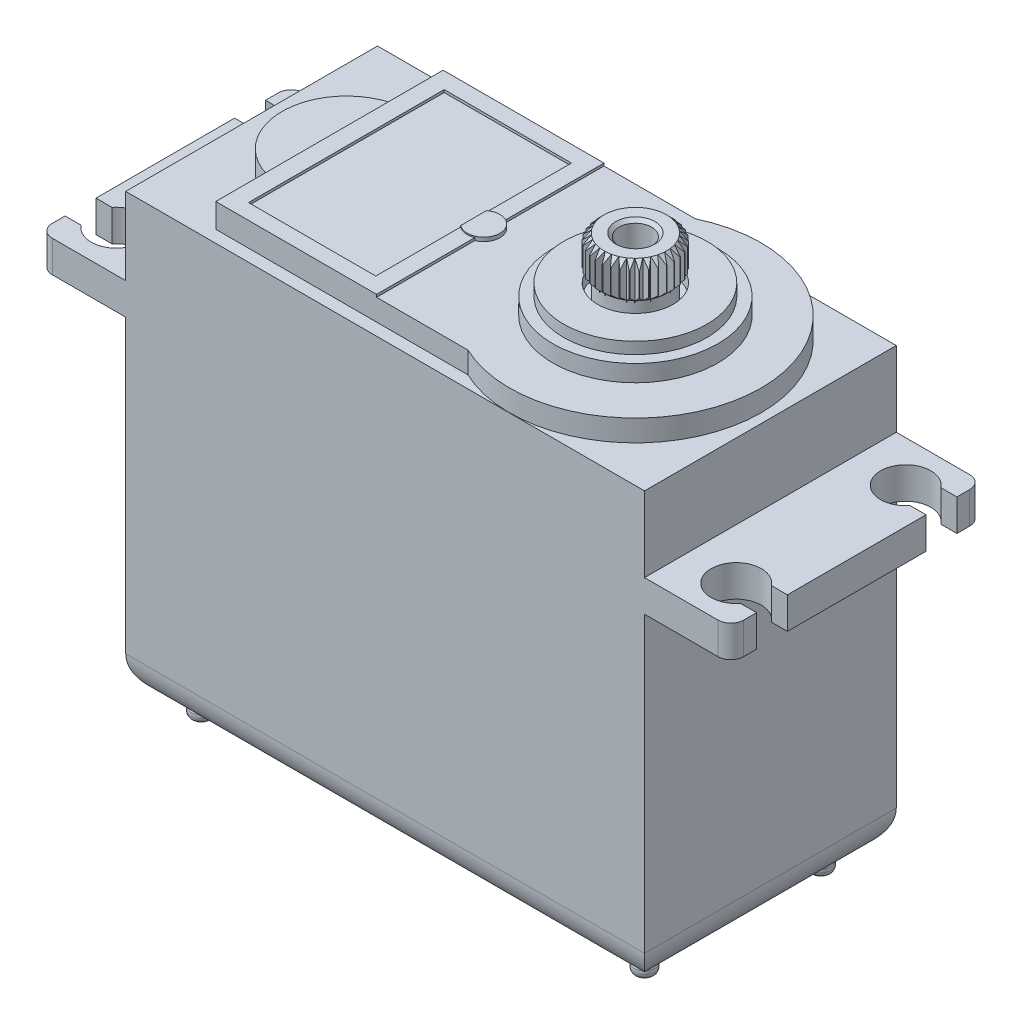
SolidWorks part; units mm, degrees
ref_plane "Front Plane" through (0, 0, 0) normal (0, 0, 1) x (1, 0, 0)
ref_plane "Top Plane" through (0, 0, 0) normal (0, 1, 0) x (1, 0, 0)
ref_plane "Right Plane" through (0, 0, 0) normal (1, 0, 0) x (0, 0, -1)
sketch "Sketch1" plane through (0, 0, 0) normal (0, 1, 0) x (1, 0, 0)
  line L1 (-18.6567, 11.3793) -> (21.6633, 11.3793)
  line L2 (-18.6567, 11.3793) -> (-18.6567, -8.1907)
  line L3 (-18.6567, -8.1907) -> (21.6633, -8.1907)
  line L4 (21.6633, 11.3793) -> (21.6633, -8.1907)
extrude "Boss-Extrude1" add sketch "Sketch1" along normal blind 35.37
sketch "Sketch2" plane through (21.6633, 0, 0) normal (1, 0, 0) x (0, 0, -1)
  line L0 (-8.1907, 0) -> (-8.1907, 3)
  line L1 (-8.1907, 35.37) -> (-8.1907, 0) construction
  line L2 (-8.1907, 3) -> (-5.1907, 0)
  line L3 (-8.1907, 0) -> (11.3793, 0) construction
  line L4 (-5.1907, 0) -> (-8.1907, 0)
  line L5 (1.5943, 0) -> (1.5943, 35.37) construction
  line L6 (-8.1907, 35.37) -> (11.3793, 35.37) construction
  line L7 (8.3793, 0) -> (11.3793, 0)
  line L8 (11.3793, 3) -> (8.3793, 0)
  line L9 (11.3793, 0) -> (11.3793, 3)
extrude "Cut-Extrude1" cut sketch "Sketch2" against normal up to next
sketch "Sketch3" plane through (0, 0, 8.1907) normal (0, 0, 1) x (1, 0, 0)
  line L0 (21.6633, 0) -> (18.6633, 0)
  line L1 (-18.6567, 0) -> (21.6633, 0) construction
  line L2 (18.6633, 0) -> (21.6633, 3)
  line L3 (21.6633, 35.37) -> (21.6633, 3) construction
  line L4 (21.6633, 3) -> (21.6633, 0)
  line L5 (1.5033, 35.37) -> (1.5033, 0) construction
  line L6 (-18.6567, 35.37) -> (21.6633, 35.37) construction
  line L7 (-18.6567, 3) -> (-18.6567, 0)
  line L8 (-15.6567, 0) -> (-18.6567, 3)
  line L9 (-18.6567, 0) -> (-15.6567, 0)
extrude "Cut-Extrude2" cut sketch "Sketch3" against normal up to next
fillet "Fillet2" radius 3 4 edges at (21.6633, 3, -1.5943) (1.5033, 3, 8.1907) (-18.6567, 3, -1.5943) (1.5033, 3, -11.3793)
sketch "Sketch5" plane through (21.6633, 0, 0) normal (1, 0, 0) x (0, 0, -1)
  line L0 (1.5943, 35.37) -> (1.5943, 29.53) construction
  line L1 (-8.1907, 35.37) -> (11.3793, 35.37) construction
  line L2 (-8.1907, 29.53) -> (1.5943, 29.53)
  line L3 (-8.1907, 35.37) -> (-8.1907, 4.2426) construction
  line L4 (1.5943, 29.53) -> (11.3793, 29.53)
  line L5 (11.3793, 35.37) -> (11.3793, 4.2426) construction
  line L6 (11.3793, 29.53) -> (11.3793, 27.07)
  line L7 (11.3793, 27.07) -> (-8.1907, 27.07)
  line L8 (-8.1907, 27.07) -> (-8.1907, 29.53)
extrude "Boss-Extrude2" add sketch "Sketch5" along normal blind 6.71
sketch "Sketch7" plane through (-18.6567, 0, 0) normal (-1, 0, 0) x (0, 0, 1)
  line L0 (-1.5943, 35.37) -> (-1.5943, 29.3613) construction
  line L1 (-11.3793, 29.3613) -> (-1.5943, 29.3613)
  line L2 (-1.5943, 29.3613) -> (8.1907, 29.3613)
  line L3 (8.1907, 29.3613) -> (8.1907, 26.9013)
  line L4 (8.1907, 26.9013) -> (-11.3793, 26.9013)
  line L5 (-11.3793, 26.9013) -> (-11.3793, 29.3613)
  line L6 (-11.3793, 35.37) -> (8.1907, 35.37) construction
  line L7 (8.1907, 35.37) -> (8.1907, 4.2426) construction
  line L8 (-11.3793, 35.37) -> (-11.3793, 4.2426) construction
extrude "Boss-Extrude3" add sketch "Sketch7" along normal blind 6.71
sketch "Sketch8" plane through (0, 29.53, 0) normal (0, 1, 0) x (1, 0, 0)
  line L0 (28.3733, 1.5943) -> (-25.3667, 1.5943) construction
  line L2 (-25.3667, -8.1907) -> (-25.3667, 11.3793) construction
  line L4 (28.3733, -3.7925) -> (27.1303, -3.7925)
  line L5 (28.3733, 11.3793) -> (28.3733, -8.1907) construction
  line L6 (28.3733, 8.181) -> (28.3733, 9.381)
  line L7 (28.3733, 9.381) -> (27.1303, 9.381)
  line L8 (28.3733, 8.181) -> (28.3733, 6.981)
  line L9 (28.3733, 6.981) -> (27.1303, 6.981)
  line L10 (28.3733, -4.9925) -> (28.3733, -3.7925)
  line L11 (28.3733, -6.1925) -> (27.1303, -6.1925)
  line L12 (28.3733, -4.9925) -> (28.3733, -6.1925)
  line L13 (1.5033, 11.3793) -> (1.5033, -8.1907) construction
  line L14 (21.6633, 11.3793) -> (-18.6567, 11.3793) construction
  line L15 (-18.6567, -8.1907) -> (21.6633, -8.1907) construction
  line L24 (-25.3667, 6.981) -> (-24.1237, 6.981)
  line L25 (-25.3667, -4.9925) -> (-25.3667, -6.1925)
  line L26 (-25.3667, -6.1925) -> (-24.1237, -6.1925)
  line L27 (-25.3667, -4.9925) -> (-25.3667, -3.7925)
  line L28 (-25.3667, -3.7925) -> (-24.1237, -3.7925)
  line L29 (-25.3667, 8.181) -> (-25.3667, 6.981)
  line L30 (-25.3667, 9.381) -> (-24.1237, 9.381)
  line L31 (-25.3667, 8.181) -> (-25.3667, 9.381)
  arc A0 (27.1303, -3.7925) -> (27.1303, -6.1925) centre (25.5933, -4.9925) ccw
  arc A1 (27.1303, 6.981) -> (27.1303, 9.381) centre (25.5933, 8.181) cw
  arc A4 (-24.1237, 6.981) -> (-24.1237, 9.381) centre (-22.5867, 8.181) ccw
  arc A5 (-24.1237, -3.7925) -> (-24.1237, -6.1925) centre (-22.5867, -4.9925) cw
extrude "Cut-Extrude3" cut sketch "Sketch8" against normal up to next
sketch "Sketch9" plane through (0, 35.37, 0) normal (0, 1, 0) x (1, 0, 0)
  line L0 (6.9933, -8.1907) -> (6.9933, -7.2426) construction
  line L1 (-18.6567, 6.4311) -> (-12.6067, 6.4311) construction
  line L2 (6.9933, 11.3793) -> (6.9933, 10.4311) construction
  line L3 (-18.6567, -3.2426) -> (-12.6067, -3.2426) construction
  line L4 (-18.6567, -8.1907) -> (-18.6567, 11.3793) construction
  line L5 (-18.6567, 1.5943) -> (21.6633, 1.5943) construction
  line L6 (-12.6067, 10.4311) -> (6.9933, 10.4311)
  line L7 (-18.6567, 11.3793) -> (-18.6567, -8.1907) construction
  line L8 (-12.6067, -7.2426) -> (-12.6067, -3.2426)
  line L9 (21.6633, -8.1907) -> (21.6633, 11.3793) construction
  line L10 (-12.6067, 10.4311) -> (-12.6067, 6.4311)
  line L11 (-12.6067, -7.2426) -> (6.9933, -7.2426)
  line L12 (21.6633, 1.5943) -> (20.9438, 1.5943) construction
  line L13 (21.6633, 11.3793) -> (-18.6567, 11.3793) construction
  arc A0 (6.9933, 10.4311) -> (6.9933, -7.2426) centre (11.1697, 1.5943) cw
  arc A1 (-12.6067, 6.4311) -> (-12.6067, -3.2426) centre (-11.2767, 1.5943) ccw
extrude "Boss-Extrude4" add sketch "Sketch9" along normal blind 1.67
sketch "Sketch10" plane through (0, 37.04, 0) normal (0, 1, 0) x (1, 0, 0)
  circle A1 centre (11.1697, 1.5943) radius 6.415
extrude "Boss-Extrude5" add sketch "Sketch10" along normal blind 1.3
sketch "Sketch11" plane through (0, 38.34, 0) normal (0, 1, 0) x (-1, 0, 0)
  circle A2 centre (-11.1697, -1.5943) radius 5.575
extrude "Boss-Extrude6" add sketch "Sketch11" along normal blind 0.9
sketch "Sketch12" plane through (0, 39.24, 0) normal (0, 1, 0) x (1, 0, 0)
  circle A1 centre (11.1697, 1.5943) radius 2.925
extrude "Cut-Extrude4" cut sketch "Sketch12" against normal blind 1
sketch "Sketch13" plane through (0, 38.24, 0) normal (0, 1, 0) x (-1, 0, 0)
  circle A0 centre (-11.1697, -1.5943) radius 2.425
extrude "Boss-Extrude7" add sketch "Sketch13" along normal blind 1.5
sketch "Sketch14" plane through (0, 39.74, 0) normal (0, 1, 0) x (1, 0, 0)
  circle A0 centre (11.1697, 1.5943) radius 2.925
extrude "Boss-Extrude8" add sketch "Sketch14" along normal blind 2.86
sketch "Sketch15" plane through (0, 42.6, 0) normal (0, 1, 0) x (1, 0, 0)
  circle A0 centre (11.1697, 1.5943) radius 1.27
extrude "Cut-Extrude5" cut sketch "Sketch15" against normal blind 7
sketch "Sketch16" plane through (0, 37.04, 0) normal (0, 1, 0) x (1, 0, 0)
  line L0 (-12.6067, -7.2426) -> (6.9933, -7.2426) construction
  line L1 (-12.6067, 10.4311) -> (-0.1067, 10.4311)
  line L2 (-12.6067, 10.4311) -> (-12.6067, -7.2426)
  line L3 (-12.6067, -7.2426) -> (-0.1067, -7.2426)
  line L4 (-0.1067, 10.4311) -> (-0.1067, -7.2426)
  line L5 (-6.3168, 9.1673) -> (-6.3567, 10.4311) construction
  line L6 (-11.2628, 9.1673) -> (-1.3708, 9.1673)
  line L7 (-11.2628, 9.1673) -> (-11.2628, -6.0433)
  line L8 (-11.2628, -6.0433) -> (-1.3708, -6.0433)
  line L9 (-1.3708, 9.1673) -> (-1.3708, 1.562)
  line L10 (-11.2628, 1.562) -> (-12.6067, 1.5943) construction
  line L11 (-1.3708, 1.562) -> (-0.1067, 1.5943) construction
  line L12 (-6.3168, -6.0433) -> (-6.3567, -7.2426) construction
  line L13 (-1.3708, 1.562) -> (-1.3708, -6.0433)
extrude "Boss-Extrude9" add sketch "Sketch16" along normal blind 0.2
sketch "Sketch17" plane through (0, 37.24, 0) normal (0, 1, 0) x (-1, 0, 0)
  line L0 (1.3708, -1.562) -> (1.3708, -2.562)
  line L1 (1.3708, 6.0433) -> (1.3708, -9.1673) construction
  line L2 (1.3708, -1.562) -> (1.3708, -0.562)
  arc A0 (1.3708, -2.562) -> (1.3708, -0.562) centre (0.592, -1.562) cw
extrude "Boss-Extrude10" add sketch "Sketch17" along normal blind 0.1 and the other way blind 0.5
sketch "Sketch19" plane through (0, 42.6, 0) normal (0, 1, 0) x (1, 0, 0)
  line L0 (10.8404, 4.5007) -> (11.3402, 4.5143) construction
  line L1 (11.3402, 4.5143) -> (11.0903, 4.0075)
  line L2 (11.0903, 4.0075) -> (10.8404, 4.5007)
  line L3 (11.0903, 4.5075) -> (11.0903, 4.0075) construction
  line L4 (10.8404, 4.5007) -> (10.7613, 4.6463)
  line L5 (11.3402, 4.5143) -> (11.4053, 4.6463)
  line L6 (10.7613, 4.6463) -> (11.4053, 4.6463)
  circle A3 centre (11.1697, 1.5943) radius 2.925 construction
  circle A4 centre (11.1697, 1.5943) radius 2.925 construction
extrude "Cut-Extrude11" cut sketch "Sketch19" against normal blind 3
sketch "Sketch21" plane through (0, 0, 0) normal (0, -1, 0) x (1, 0, 0)
  line L0 (1.5033, 5.1907) -> (1.5033, -8.3793) construction
  line L1 (20.7846, 7.3121) -> (17.7846, 7.3121)
  line L2 (20.7846, 7.3121) -> (20.7846, 4.3121)
  line L3 (20.7846, 4.3121) -> (17.7846, 4.3121)
  line L4 (17.7846, 7.3121) -> (17.7846, 4.3121)
  line L5 (-15.6567, 5.1907) -> (18.6633, 5.1907) construction
  line L6 (-15.6567, -8.3793) -> (18.6633, -8.3793) construction
  line L7 (-15.6567, -1.5943) -> (18.6633, -1.5943) construction
  line L8 (-15.6567, -8.3793) -> (-15.6567, 5.1907) construction
  line L9 (18.6633, -8.3793) -> (18.6633, 5.1907) construction
  line L10 (17.7846, -10.5006) -> (17.7846, -7.5006)
  line L11 (20.7846, -7.5006) -> (17.7846, -7.5006)
  line L12 (20.7846, -10.5006) -> (20.7846, -7.5006)
  line L13 (20.7846, -10.5006) -> (17.7846, -10.5006)
  line L14 (-17.778, -7.5006) -> (-14.778, -7.5006)
  line L15 (-14.778, -10.5006) -> (-14.778, -7.5006)
  line L16 (-14.778, 7.3121) -> (-14.778, 4.3121)
  line L17 (-17.778, 4.3121) -> (-14.778, 4.3121)
  line L18 (-17.778, -10.5006) -> (-14.778, -10.5006)
  line L19 (-17.778, -10.5006) -> (-17.778, -7.5006)
  line L20 (-17.778, 7.3121) -> (-17.778, 4.3121)
  line L21 (-17.778, 7.3121) -> (-14.778, 7.3121)
extrude "Cut-Extrude12" cut sketch "Sketch21" against normal blind 1
fillet "Fillet4" radius 1 4 edges at (-14.778, 0.5, -7.5006) (-14.778, 0.5, 4.3121) (17.7846, 0.5, -7.5006) (17.7846, 0.5, 4.3121)
fillet "Fillet5" radius 1 4 edges at (-25.3667, 28.1313, 8.1907) (-25.3667, 28.1313, -11.3793) (28.3733, 28.3, -11.3793) (28.3733, 28.3, 8.1907)
chamfer "Chamfer2" distance 0.5 angle 45 2 edges at (11.2493, 42.6, 1.3297) (11.2493, 39.74, 1.3297)
chamfer "Chamfer3" distance 0.25 angle 45 1 edges at (11.1697, 42.6, -0.3243)
pattern_circular "CirPattern12" count 34 over 360 about axis through (11.1697, 42.6, -1.5943) along (0, -1, 0) of "Cut-Extrude11"
sketch "Sketch23" plane through (0, 1, 0) normal (0, -1, 0) x (1, 0, 0)
  line L0 (1.5033, 5.1907) -> (1.5033, -8.3793) construction
  line L1 (-14.7854, 5.1907) -> (17.792, 5.1907) construction
  line L2 (-14.7854, -8.3793) -> (17.792, -8.3793) construction
  line L3 (18.6633, -1.5943) -> (-15.6567, -1.5943) construction
  line L4 (18.6633, -7.508) -> (18.6633, 4.3195) construction
  line L5 (-15.6567, -7.508) -> (-15.6567, 4.3195) construction
  circle A0 centre (18.7344, -8.4503) radius 0.4237
  circle A1 centre (18.7344, 5.2618) radius 0.4237
  circle A2 centre (-15.7278, 5.2618) radius 0.4237
  circle A3 centre (-15.7278, -8.4503) radius 0.4237
extrude "Boss-Extrude12" add sketch "Sketch23" along normal blind 0.1
sketch "Sketch24" plane through (0, 0.9, 0) normal (0, -1, 0) x (1, 0, 0)
  line L0 (1.5033, 5.1907) -> (1.5033, -8.3793) construction
  line L1 (-14.7854, 5.1907) -> (17.792, 5.1907) construction
  line L2 (-14.7854, -8.3793) -> (17.792, -8.3793) construction
  line L3 (18.6633, -1.5943) -> (-15.6567, -1.5943) construction
  line L4 (18.6633, -7.508) -> (18.6633, 4.3195) construction
  line L5 (-15.6567, -7.508) -> (-15.6567, 4.3195) construction
  circle A0 centre (18.7344, -8.4503) radius 0.8
  circle A1 centre (18.7344, 5.2618) radius 0.8
  circle A2 centre (-15.7278, 5.2618) radius 0.8
  circle A3 centre (-15.7278, -8.4503) radius 0.8
extrude "Boss-Extrude13" add sketch "Sketch24" along normal blind 0.9
fillet "Fillet8" radius 0.45 4 edges at (18.7344, 0, -9.2503) (-15.7278, 0, -7.6503) (-15.7278, 0, 4.4618) (18.7344, 0, 6.0618)
fillet "Fillet9" radius 0.2 4 edges at (-15.7278, 0.9, -7.6503) (-15.7278, 0.9, 4.4618) (18.7344, 0.9, 6.0618) (18.7344, 0.9, -9.2503)
sketch "Sketch25" plane through (0, 0, 0) normal (0, -1, 0) x (1, 0, 0)
  line L0 (18.0844, 5.3868) -> (18.0844, 5.1368)
  line L1 (18.6094, 4.6118) -> (18.8594, 4.6118)
  line L2 (18.0844, 5.3868) -> (18.6094, 5.3868)
  line L3 (18.6094, 5.3868) -> (18.6094, 5.9118)
  line L4 (19.3844, 5.1368) -> (19.3844, 5.3868)
  line L5 (18.8594, 5.9118) -> (18.6094, 5.9118)
  line L6 (1.5033, 5.1907) -> (1.5033, -8.3793) construction
  line L7 (-14.7854, 5.1907) -> (17.792, 5.1907) construction
  line L8 (-14.7854, -8.3793) -> (17.792, -8.3793) construction
  line L9 (18.6633, -1.5943) -> (-15.6567, -1.5943) construction
  line L10 (18.6633, -7.508) -> (18.6633, 4.3195) construction
  line L11 (-15.6567, -7.508) -> (-15.6567, 4.3195) construction
  line L12 (18.6094, -8.3253) -> (18.0844, -8.3253)
  line L13 (18.6094, -7.8003) -> (18.6094, -8.3253)
  line L14 (18.8594, -8.3253) -> (18.8594, -7.8003)
  line L15 (19.3844, -8.3253) -> (18.8594, -8.3253)
  line L16 (18.8594, -8.5753) -> (19.3844, -8.5753)
  line L17 (18.8594, 5.9118) -> (18.8594, 5.3868)
  line L18 (18.8594, 5.3868) -> (19.3844, 5.3868)
  line L19 (18.8594, -9.1003) -> (18.8594, -8.5753)
  line L20 (19.3844, 5.1368) -> (18.8594, 5.1368)
  line L21 (18.8594, 5.1368) -> (18.8594, 4.6118)
  line L22 (18.8594, -9.1003) -> (18.6094, -9.1003)
  line L23 (18.6094, 4.6118) -> (18.6094, 5.1368)
  line L24 (18.6094, 5.1368) -> (18.0844, 5.1368)
  line L25 (19.3844, -8.3253) -> (19.3844, -8.5753)
  line L26 (18.6094, -8.5753) -> (18.6094, -9.1003)
  line L27 (18.0844, -8.5753) -> (18.6094, -8.5753)
  line L28 (18.6094, -7.8003) -> (18.8594, -7.8003)
  line L29 (18.0844, -8.5753) -> (18.0844, -8.3253)
  line L30 (-15.0778, -8.5753) -> (-15.0778, -8.3253)
  line L31 (-15.6028, -7.8003) -> (-15.8528, -7.8003)
  line L32 (-15.0778, -8.5753) -> (-15.6028, -8.5753)
  line L33 (-15.6028, -8.5753) -> (-15.6028, -9.1003)
  line L34 (-16.3778, -8.3253) -> (-16.3778, -8.5753)
  line L35 (-15.6028, 5.1368) -> (-15.0778, 5.1368)
  line L36 (-15.6028, 4.6118) -> (-15.6028, 5.1368)
  line L37 (-15.8528, -9.1003) -> (-15.6028, -9.1003)
  line L38 (-15.8528, 5.1368) -> (-15.8528, 4.6118)
  line L39 (-16.3778, 5.1368) -> (-15.8528, 5.1368)
  line L40 (-15.8528, -9.1003) -> (-15.8528, -8.5753)
  line L41 (-15.8528, 5.3868) -> (-16.3778, 5.3868)
  line L42 (-15.8528, 5.9118) -> (-15.8528, 5.3868)
  line L43 (-15.8528, -8.5753) -> (-16.3778, -8.5753)
  line L44 (-16.3778, -8.3253) -> (-15.8528, -8.3253)
  line L45 (-15.8528, -8.3253) -> (-15.8528, -7.8003)
  line L46 (-15.6028, -7.8003) -> (-15.6028, -8.3253)
  line L47 (-15.6028, -8.3253) -> (-15.0778, -8.3253)
  line L48 (-15.8528, 5.9118) -> (-15.6028, 5.9118)
  line L49 (-16.3778, 5.1368) -> (-16.3778, 5.3868)
  line L50 (-15.6028, 5.3868) -> (-15.6028, 5.9118)
  line L51 (-15.0778, 5.3868) -> (-15.6028, 5.3868)
  line L52 (-15.6028, 4.6118) -> (-15.8528, 4.6118)
  line L53 (-15.0778, 5.3868) -> (-15.0778, 5.1368)
extrude "Cut-Extrude14" cut sketch "Sketch25" against normal blind 0.6
sketch "Croquis1" plane through (0, 42.6, 0) normal (0, 1, 0) x (1, 0, 0)
  circle A0 centre (11.1697, 1.5943) radius 2.925
